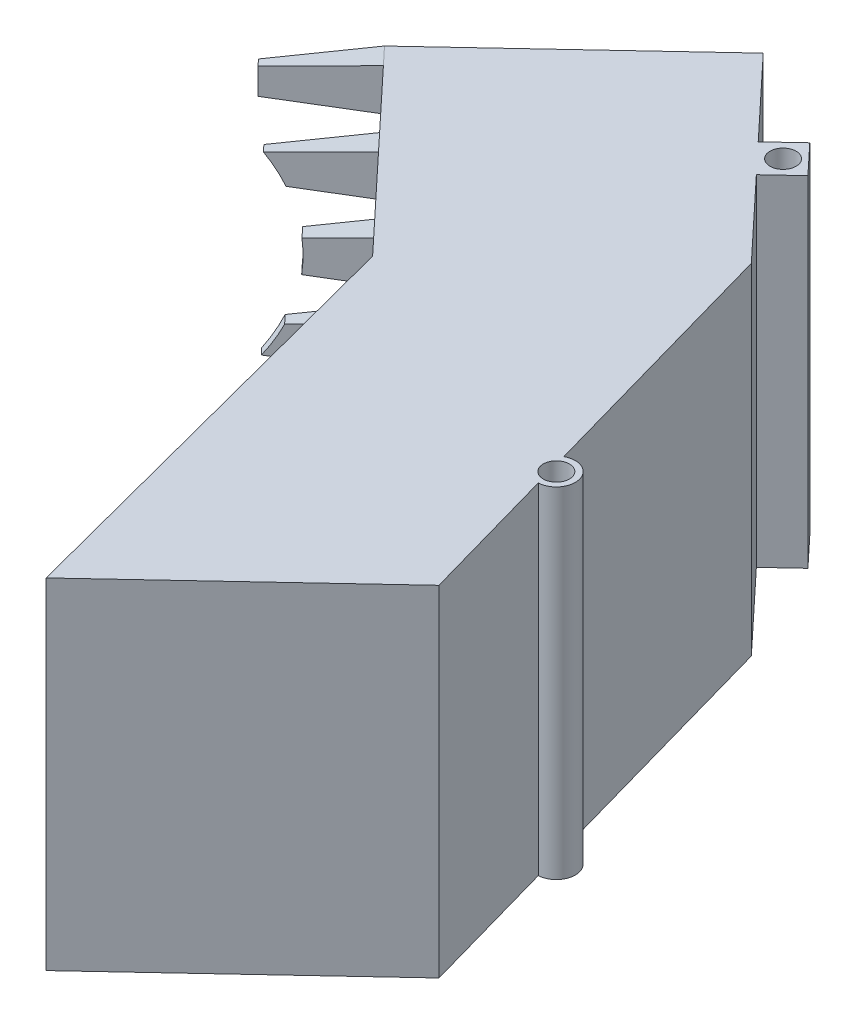
SolidWorks part; units mm, degrees
ref_plane "Front Plane" through (0, 0, 0) normal (0, 0, 1) x (1, 0, 0)
ref_plane "Top Plane" through (0, 0, 0) normal (0, 1, 0) x (1, 0, 0)
ref_plane "Right Plane" through (0, 0, 0) normal (1, 0, 0) x (0, 0, -1)
sketch "Sketch1" plane through (0, 0, 0) normal (0, 1, 0) x (1, 0, 0)
  line L0 (-4.2088, -43.4753) -> (11.4751, 13.8639) construction
  line L1 (15.2438, 108.2324) -> (-2.7837, 127.4797) construction
  line L2 (-27.496, 153.8638) -> (-74.9669, 109.4011) construction
  line L3 (11.4751, 13.8639) -> (-32.8086, 77.4293) construction
  line L4 (15.2438, 108.2324) -> (33.1183, 44.8363) construction
  line L5 (45.0177, 2.6318) -> (-4.2088, -43.4753) construction
  line L6 (-4.2088, -43.4753) -> (-32.2271, 63.7697) construction
  line L7 (45.0177, 2.6318) -> (35.5507, 36.2092)
  line L8 (15.2438, 108.2324) -> (-2.7837, 127.4797)
  line L9 (-27.496, 153.8638) -> (-74.9669, 109.4011)
  line L10 (-74.9669, 109.4011) -> (-32.2271, 63.7697)
  line L11 (-32.2271, 63.7697) -> (-4.2088, -43.4753)
  line L13 (45.0177, 2.6318) -> (-4.2088, -43.4753)
  line L15 (35.5507, 36.2092) -> (45.0177, 2.6318) construction
  line L16 (33.1183, 44.8363) -> (15.2438, 108.2324)
  line L17 (-32.8086, 77.4293) -> (-1.2, 109.0418) construction
  line L18 (20.4045, -20.4217) -> (11.4751, 13.8639) construction
  line L19 (-4.2088, -43.4753) -> (-17.3046, 6.6513) construction
  line L20 (0.3363, 130.3833) -> (0.3273, 130.3935) construction
  line L21 (-17.3046, 6.6513) -> (11.4751, 13.8639) construction
  line L22 (-6.1168, 137.7559) -> (-9.4684, 134.6166) construction
  line L23 (-3.0026, 140.4816) -> (-2.8851, 140.5844) construction
  line L24 (-17.3046, 6.6513) -> (-13.163, 7.6893) construction
  line L25 (-13.163, 7.6893) -> (-27.9465, 65.5328) construction
  line L26 (3.679, 133.5328) -> (-2.7837, 127.4797)
  line L27 (3.679, 133.5328) -> (-3.0057, 140.6698)
  line L29 (-3.0057, 140.6698) -> (-9.4684, 134.6166)
  line L30 (-51.2315, 131.6325) -> (-48.4968, 128.2564) construction
  line L31 (-48.4968, 128.2564) -> (-27.496, 147.9264) construction
  line L32 (-9.4684, 134.6166) -> (-27.496, 153.8638) construction
  line L33 (-9.4684, 134.6166) -> (-27.496, 153.8638)
  line L34 (-3.0026, 140.4816) -> (-3.0057, 140.6698) construction
  line L35 (-27.496, 147.9264) -> (-23.2222, 143.3634) construction
  line L36 (0.3273, 130.3935) -> (0.3363, 130.3833) construction
  line L37 (-23.2222, 143.3634) -> (-20.2598, 146.1381) construction
  line L38 (-23.2222, 143.3634) -> (9.6827, 108.2324) construction
  line L39 (24.1811, 76.5343) -> (20.2695, 75.4315) construction
  line L40 (20.2695, 75.4315) -> (13.2737, 100.2435) construction
  line L41 (20.2695, 75.4315) -> (27.658, 49.2262) construction
  line L42 (27.658, 49.2262) -> (31.4686, 35.7107) construction
  line L43 (31.4686, 35.7107) -> (34.5448, 24.4916) construction
  line L44 (12.1112, 105.39) -> (13.2737, 100.2435) construction
  line L45 (9.6827, 108.2324) -> (12.1112, 105.39) construction
  line L46 (-53.597, 86.5854) -> (-50.4371, 89.545) construction
  line L47 (-50.4371, 89.545) -> (-71.8071, 112.3607) construction
  line L48 (-48.4968, 128.2564) -> (-68.8447, 109.1979) construction
  line L49 (-68.8447, 109.1979) -> (-50.4371, 89.545) construction
  line L50 (-50.4371, 89.545) -> (-27.9465, 65.5328) construction
  line L51 (-68.8447, 109.1979) -> (-27.9465, 65.5328)
  line L52 (-27.9465, 65.5328) -> (-13.163, 7.6893)
  line L53 (-68.8447, 109.1979) -> (-27.496, 147.9264)
  line L54 (-27.496, 147.9264) -> (12.1112, 105.39)
  line L55 (12.1112, 105.39) -> (34.5448, 24.4916)
  arc A1 (35.5507, 36.2092) -> (33.1183, 44.8363) centre (35.3343, 40.8046) ccw
  circle A4 centre (-2.8946, 134.0748) radius 3.175
  circle A5 centre (35.3343, 40.8046) radius 3.175
  circle A6 centre (11.4751, 13.8639) radius 25.4
  circle A7 centre (-32.8086, 77.4293) radius 3.175
  circle A8 centre (-1.2, 109.0418) radius 3.175
  point P30 (0, 0)
  dimension "D1" = 6.35
  dimension "D2" = 6.35
  dimension "D3" = 59.4455
  dimension "D5" = 50.8
  dimension "D8" = 6.35
  dimension "D4" = 31.576
  dimension "D6" = 77.47
  dimension "D7" = 129.839
  dimension "D9" = 44.704
  dimension "D10" = 100.14
  dimension "D11" = 35.4294
  dimension "D12" = 4.2697
ref_plane "Plane1" through (0, 0, 0) normal (0, 1, 0) x (1, 0, 0)
sketch "Sketch4" plane through (0, 0, 0) normal (0, 1, 0) x (1, 0, 0)
  line L0 (-68.8447, 109.1979) -> (-27.9465, 65.5328)
  line L1 (-27.9465, 65.5328) -> (-13.1495, 7.6432)
  line L2 (-68.8447, 109.1979) -> (-27.496, 147.9264)
  line L3 (-27.496, 147.9264) -> (12.1112, 105.39)
  line L4 (12.1112, 105.39) -> (34.5583, 24.4455)
  circle A0 centre (-2.8946, 134.0748) radius 3.175
  circle A1 centre (35.3343, 40.8046) radius 3.175
  circle A2 centre (11.4751, 13.8639) radius 25.393
  circle A3 centre (-32.8086, 77.4293) radius 3.175
  circle A4 centre (-1.2, 109.0418) radius 3.175
  point P16 (-27.496, 147.9264)
  point P18 (-68.8447, 109.1979)
  point P20 (-27.9465, 65.5328)
  point P22 (35.3343, 40.8046)
  point P24 (12.1112, 105.39)
  point P26 (-2.8946, 134.0748)
  point P28 (-1.2, 109.0418)
  point P30 (-32.8086, 77.4293)
  point P32 (11.4751, 13.8639)
extrude "Boss-Extrude2" add sketch "Sketch1" along normal blind 76.2 contours L7 A1 L16 L8 L26 L27 L29 L33 L9 L10 L11 L13 A6 L52 L51 L53 L54 L55 A5 A4 region at (18.8257, 0, 18.7361)
extrude "Boss-Extrude3" add sketch "Sketch1<5>" along normal blind 6.35 contours A6 L55 L54 L53 L51 L52 A8 A7 region at (-15.1101, 0, -86.0279)
sketch "Sketch1<5>" plane through (0, 0, 0) normal (0, 1, 0) x (1, 0, 0) same geometry as "Sketch1"
ref_plane "Plane2" through (0, 76.2, 0) normal (0, 1, 0) x (1, 0, 0)
sketch "Sketch5" plane through (0, 76.2, 0) normal (0, 1, 0) x (1, 0, 0)
  line L0 (45.0177, 2.6318) -> (35.5507, 36.2092)
  line L1 (15.2438, 108.2324) -> (-2.7837, 127.4797)
  line L2 (-27.496, 153.8638) -> (-74.9669, 109.4011)
  line L3 (-74.9669, 109.4011) -> (-32.2271, 63.7697)
  line L4 (-32.2271, 63.7697) -> (-4.2088, -43.4753)
  line L5 (45.0177, 2.6318) -> (-4.2088, -43.4753)
  line L6 (33.1183, 44.8363) -> (15.2438, 108.2324)
  line L7 (3.679, 133.5328) -> (-2.7837, 127.4797)
  line L8 (3.679, 133.5328) -> (-3.0057, 140.6698)
  line L9 (-3.0057, 140.6698) -> (-9.4684, 134.6166)
  line L10 (-9.4684, 134.6166) -> (-27.496, 153.8638)
  line L11 (45.0177, 2.6318) -> (35.5507, 36.2092) construction
  line L12 (-74.9669, 109.4011) -> (-32.2271, 63.7697) construction
  circle A1 centre (-2.8946, 134.0748) radius 3.175
  arc A3 (35.5507, 36.2092) -> (33.1183, 44.8363) centre (35.3343, 40.8046) ccw construction
  arc A4 (35.5507, 36.2092) -> (33.1183, 44.8363) centre (35.3343, 40.8046) ccw
  circle A5 centre (35.3343, 40.8046) radius 3.175
extrude "Boss-Extrude4" add sketch "Sketch5" along normal blind 6.35
ref_plane "Plane3" through (14.6497, 0, -13.7214) normal (-0.7299, 0, 0.6836) x (0.6836, 0, 0.7299)
sketch "Sketch6" plane through (14.6497, 0, -13.7214) normal (-0.7299, 0, 0.6836) x (0.6836, 0, 0.7299)
  line L0 (-99.8337, 82.55) -> (-99.8337, 0) construction
  line L4 (-99.8337, 66.675) -> (-99.8337, 15.875) construction
  line L6 (-125.2337, 66.675) -> (-74.4337, 66.675)
  line L7 (-125.2337, 66.675) -> (-125.2337, 15.875)
  line L8 (-125.2337, 15.875) -> (-74.4337, 15.875)
  line L9 (-74.4337, 66.675) -> (-74.4337, 15.875)
  line L11 (-131.0944, 82.55) -> (-68.573, 82.55) construction
  line L12 (65.9916, 0) -> (-65.9916, 0) construction
  line L13 (-131.0944, 41.275) -> (-68.573, 41.275) construction
  line L14 (-131.0944, 82.55) -> (-131.0944, 0) construction
  line L15 (-68.573, 82.55) -> (-68.573, 0) construction
  line L16 (-125.2337, 41.275) -> (-74.4337, 41.275) construction
  point P4 (-99.8337, 82.55)
  point P6 (-131.0944, 41.275)
  point P20 (-99.8337, 41.275)
  point P23 (-99.8337, 41.275)
  dimension "D1" = 50.8
  dimension "D2" = 50.8
extrude "Cut-Extrude1" cut sketch "Sketch6" against normal blind 21.59
sketch "Sketch7" plane through (14.6497, 0, -13.7214) normal (-0.7299, 0, 0.6836) x (0.6836, 0, 0.7299)
  line L0 (-125.2337, 66.675) -> (-125.2337, 15.875) construction
  line L1 (-131.0944, 82.55) -> (-125.2337, 82.55)
  line L2 (-131.0944, 82.55) -> (-131.0944, 72.39)
  line L3 (-131.0944, 72.39) -> (-125.2337, 72.39)
  line L4 (-125.2337, 82.55) -> (-125.2337, 72.39)
  line L5 (-131.0944, 54.2925) -> (-125.2337, 54.2925)
  line L6 (-125.2337, 64.4525) -> (-125.2337, 54.2925)
  line L7 (-131.0944, 64.4525) -> (-125.2337, 64.4525)
  line L8 (-131.0944, 64.4525) -> (-131.0944, 54.2925)
  line L9 (-131.0944, 36.195) -> (-125.2337, 36.195)
  line L10 (-125.2337, 46.355) -> (-125.2337, 36.195)
  line L11 (-131.0944, 46.355) -> (-125.2337, 46.355)
  line L12 (-131.0944, 46.355) -> (-131.0944, 36.195)
  line L13 (-131.0944, 18.0975) -> (-125.2337, 18.0975)
  line L14 (-125.2337, 28.2575) -> (-125.2337, 18.0975)
  line L15 (-131.0944, 28.2575) -> (-125.2337, 28.2575)
  line L16 (-131.0944, 28.2575) -> (-131.0944, 18.0975)
  line L17 (-131.0944, 0) -> (-125.2337, 0)
  line L18 (-125.2337, 10.16) -> (-125.2337, 0)
  line L19 (-131.0944, 10.16) -> (-125.2337, 10.16)
  line L20 (-131.0944, 10.16) -> (-131.0944, 0)
  line L21 (-131.0944, 0) -> (-68.573, 0) construction
  point P7 (0, 0)
  dimension "D1" = 10.16
  dimension "D2" = 5
extrude "Boss-Extrude5" add sketch "Sketch7" along normal blind 21.59 draft 5
ref_plane "Plane4" through (-89.6167, 0, -95.6796) normal (-0.6836, 0, -0.7299) x (-0.7299, 0, 0.6836)
sketch "Sketch10" plane through (-89.6167, 0, -95.6796) normal (-0.6836, 0, -0.7299) x (-0.7299, 0, 0.6836)
  circle A0 centre (29.8207, 41.5477) radius 36.0519
  point P0 (15.9271, 42.0477)
extrude "Cut-Extrude2" cut sketch "Sketch10" against normal blind 21.59
